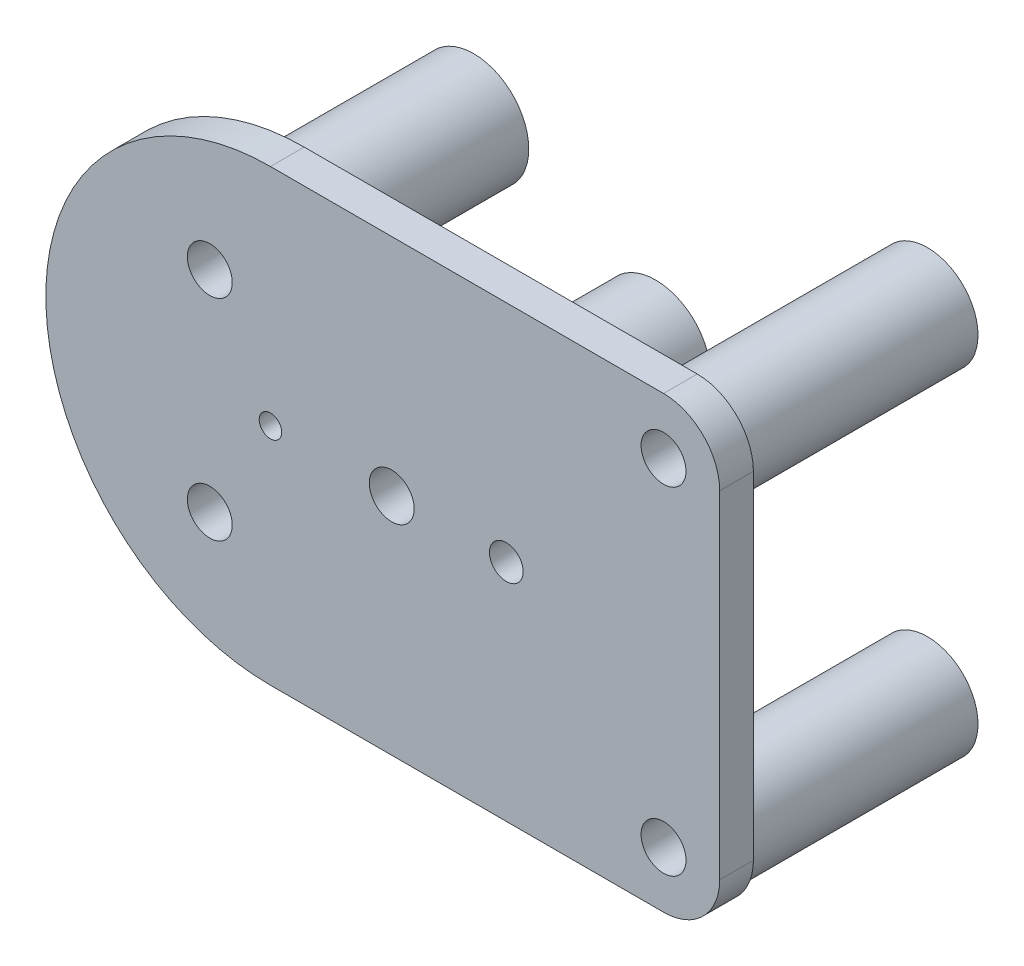
SolidWorks part; units mm, degrees
ref_plane "Ebene vorne" through (0, 0, 0) normal (0, 0, 1) x (1, 0, 0)
ref_plane "Ebene oben" through (0, 0, 0) normal (0, 1, 0) x (1, 0, 0)
ref_plane "Ebene rechts" through (0, 0, 0) normal (1, 0, 0) x (0, 0, -1)
sketch "Skizze1" plane through (0, 0, 0) normal (0, 0, 1) x (1, 0, 0)
  line L0 (0, 20) -> (40, 20)
  line L1 (0, -20) -> (40, -20)
  line L2 (40, 20) -> (40, -20)
  line L3 (0, 0) -> (40, 0) construction
  circle A0 centre (0, 0) radius 20
  circle A1 centre (0, 0) radius 1
  circle A2 centre (21, 0) radius 1.5
  circle A3 centre (35, 15) radius 2
  circle A4 centre (35, -15) radius 2
  dimension "D1" = 40
  dimension "D2" = 2
  dimension "D4" = 3
  dimension "D6" = 4
  dimension "D3" = 40
  dimension "D5" = 21
  dimension "D7" = 5
  dimension "D8" = 5
extrude "Aufsatz-Linear austragen1" add sketch "Skizze1" along normal blind 3 contours A1 A2 A0 | L3 A2 A0 L1 L2 | A2 L3 L2 L0 A0 region at (13.3623, 14.112, 0) region at (27.2842, 10.9393, 0) region at (27.2842, -10.9393, 0)
sketch "Skizze2" plane through (0, 0, 0) normal (0, 0, -1) x (-1, 0, 0)
  line L0 (0, 0) -> (-10.8, 0) construction
  line L1 (0, 0) -> (0, 5) construction
  circle A0 centre (-10.8, 0) radius 4.9
  circle A2 centre (5.4, 9.3531) radius 4.9
  circle A3 centre (5.4, -9.3531) radius 4.9
  point P11 (0, 0)
  dimension "D1" = 9.8
  dimension "D2" = 10.8
  dimension "D3" = 5
  dimension "D5" = 10.8
  dimension "D6" = 10.8
  dimension "D4" = 3
extrude "Aufsatz-Linear austragen2" add sketch "Skizze2" along normal blind 20.5
sketch "Skizze3" plane through (0, 0, -20.5) normal (0, 0, -1) x (-1, 0, 0)
  circle A0 centre (-10.8, 0) radius 2
  circle A3 centre (5.4, 9.3531) radius 2
  circle A4 centre (5.4, -9.3531) radius 2
  point P9 (0.35, 0.2021)
  point P10 (0, 0)
  dimension "D1" = 4
  dimension "D2" = 3
extrude "Schnitt-Linear austragen1" cut sketch "Skizze3" against normal through all
fillet "Verrundung1" radius 5 2 edges at (40, -20, 1.5) (40, 20, 1.5)
sketch "Skizze4" plane through (0, 0, 0) normal (0, 0, -1) x (-1, 0, 0)
  circle A0 centre (-35, 15) radius 2
  circle A1 centre (-35, 15) radius 4.5
  circle A2 centre (-35, -15) radius 2
  circle A3 centre (-35, -15) radius 4.5
  dimension "D1" = 4
  dimension "D2" = 9
  dimension "D3" = 9
  dimension "D4" = 4
extrude "Aufsatz-Linear austragen3" add sketch "Skizze4" along normal up to surface (20.5 mm away) up to face at (8.8, 0, -20.5)
